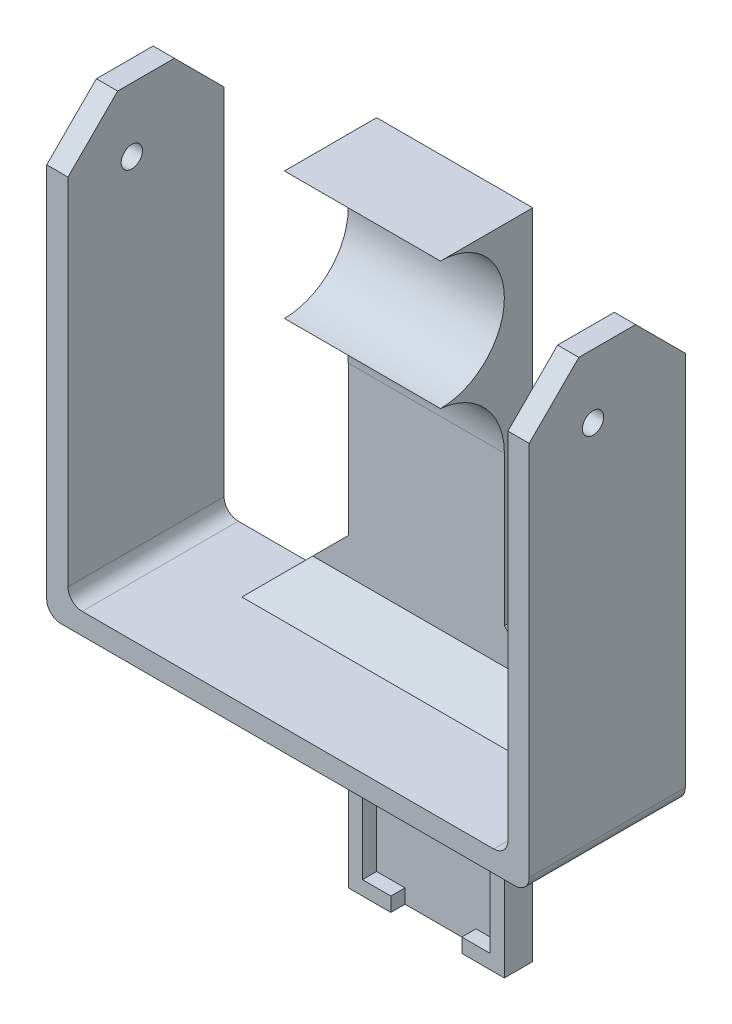
SolidWorks part; units mm, degrees
ref_plane "Front Plane" through (0, 0, 0) normal (0, 0, 1) x (1, 0, 0)
ref_plane "Top Plane" through (0, 0, 0) normal (0, 1, 0) x (1, 0, 0)
ref_plane "Right Plane" through (0, 0, 0) normal (1, 0, 0) x (0, 0, -1)
sketch "Sketch1" plane through (0, 0, 0) normal (0, 0, 1) x (1, 0, 0)
  line L0 (-2, -2) -> (20, -2)
  line L1 (0, 0) -> (18, 0)
  line L2 (0, 0) -> (0, 28)
  line L3 (0, 28) -> (18, 28)
  line L4 (18, 0) -> (18, 28)
  line L5 (4, 3.1262) -> (14, 3.1262)
  line L6 (4, 3.1262) -> (4, -8.2744)
  line L7 (4, -8.2744) -> (14, -8.2744)
  line L8 (14, 3.1262) -> (14, -8.2744)
  line L9 (20, -2) -> (20, 30)
  line L10 (-2, 30) -> (20, 30)
  line L11 (-2, -2) -> (-2, 30)
  point P9 (9, -8.2744)
  point P10 (9, 28)
  dimension "D1" = 18
  dimension "D2" = 28
  dimension "D3" = 10
  dimension "D4" = 2
extrude "Boss-Extrude1" add sketch "Sketch1" along normal blind 2 contours L11 L0 L6 L1 L2 L3 L4 L8 L9 L10 region at (-1.6117, 14, 0)
sketch "Sketch2" plane through (0, 0, 0) normal (0, 0, -1) x (-1, 0, 0)
  line L1 (-20, 30) -> (2, 30)
  line L2 (-20, 30) -> (-20, -2)
  line L3 (-20, -2) -> (2, -2)
  line L4 (2, 30) -> (2, -2)
extrude "Boss-Extrude2" add sketch "Sketch2" along normal blind 2
sketch "Sketch3" plane through (0, 0, 0) normal (0, 0, 1) x (1, 0, 0)
  line L1 (-2, 30) -> (20, 30)
  line L2 (-2, 30) -> (-2, 90)
  line L3 (-2, 90) -> (20, 90)
  line L4 (20, 30) -> (20, 90)
  point P5 (20, 30)
  dimension "D1" = 60
extrude "Boss-Extrude3" add sketch "Sketch3" along normal blind 2 and the other way blind 2
sketch "Sketch4" plane through (0, 0, 2) normal (0, 0, 1) x (1, 0, 0)
  line L0 (14, -2) -> (4, -2) construction
  line L1 (-23.5, 31) -> (41.5, 31)
  line L2 (-23.5, 31) -> (-23.5, 28)
  line L3 (-23.5, 28) -> (41.5, 28)
  line L4 (41.5, 31) -> (41.5, 28)
  line L5 (0, 28) -> (18, 28) construction
  line L7 (-23.5, 28) -> (-26.5, 28)
  line L8 (-23.5, 28) -> (-23.5, 90)
  line L9 (-23.5, 90) -> (-26.5, 90)
  line L10 (-26.5, 28) -> (-26.5, 90)
  line L11 (41.5, 28) -> (38.5, 28)
  line L12 (41.5, 28) -> (41.5, 90)
  line L13 (41.5, 90) -> (38.5, 90)
  line L14 (38.5, 28) -> (38.5, 90)
  point P4 (9, 31)
  point P7 (9, -2)
  point P16 (-23.5, 92.2784)
  point P17 (0, 0)
  point P19 (0, 0)
  line M10 (-2, 90) -> (-2, -2)
  line M15 (0, 28) -> (18, 28)
  line M20 (20, -2) -> (20, 90)
  dimension "D1" = 65
  dimension "D2" = 3
  dimension "D3" = 3
  dimension "D4" = 3
extrude "Boss-Extrude4" add sketch "Sketch4" along normal blind 18 and the other way blind 4 contours L10 L7 L2 L8 L9 | L2 L3 L1 M10 | L3 L14 L1 M20 | L14 L1 L12 L13 | L3 L1 M10 M15 M20 | L14 L3 L4 L1 region at (-12.75, 29.5, 2) region at (-25, 59, 2) region at (9, 29.5, 2) region at (29.25, 29.5, 2) region at (40, 60.5, 2) region at (40, 29.5, 2)
sketch "Sketch5" plane through (20, 0, 0) normal (1, 0, 0) x (0, 0, -1)
  line L0 (2, 28) -> (2, 90) construction
  line L1 (2, 90) -> (-20, 90) construction
  line L2 (-11, 72) -> (-2, 72)
  line L3 (-2, 72) -> (1.0136, 83.2532)
  line L4 (1.0136, 83.2532) -> (-2, 90)
  line L5 (-2, 90) -> (-11, 90)
  circle A0 centre (-11, 81) radius 9
  line M5 (-2, 90) -> (-2, 31)
  dimension "D2" = 18
  dimension "D1" = 13
extrude "Boss-Extrude5" add sketch "Sketch5" against normal blind 22 contours A0 L2 M5 | A0 L5 M5 region at (20, 74.0103, 4.0103) region at (20, 87.9897, 4.0103)
fillet "Fillet1" radius 10 1 edges at (9, 72, 2)
chamfer "Chamfer1" distance 7 angle 45 4 edges at (-25, 90, -2) (-25, 90, 20) (40, 90, -2) (40, 90, 20)
sketch "Sketch6" plane through (41.5, 0, 0) normal (1, 0, 0) x (0, 0, -1)
  line L0 (-5, 90) -> (-13, 90) construction
  line L1 (-20, 28) -> (-20, 83) construction
  circle A0 centre (-11, 81) radius 1.5
  point P4 (0, 0)
  dimension "D2" = 3
  dimension "D1" = 9
  dimension "D3" = 9
extrude "Cut-Extrude1" cut sketch "Sketch6" against normal blind 72
fillet "Fillet2" radius 2 4 edges at (-26.5, 28, 9) (41.5, 28, 9) (38.5, 31, 9) (-23.5, 31, 9)
chamfer "Chamfer2" distance 10 angle 45 2 edges at (-2, 28, 0) (20, 28, 0)
chamfer "Chamfer3" distance 10 angle 45 2 edges at (20, 31, 0) (-2, 31, 0)
chamfer "Chamfer4" distance 5 angle 45 1 edges at (9, 31, 2)
